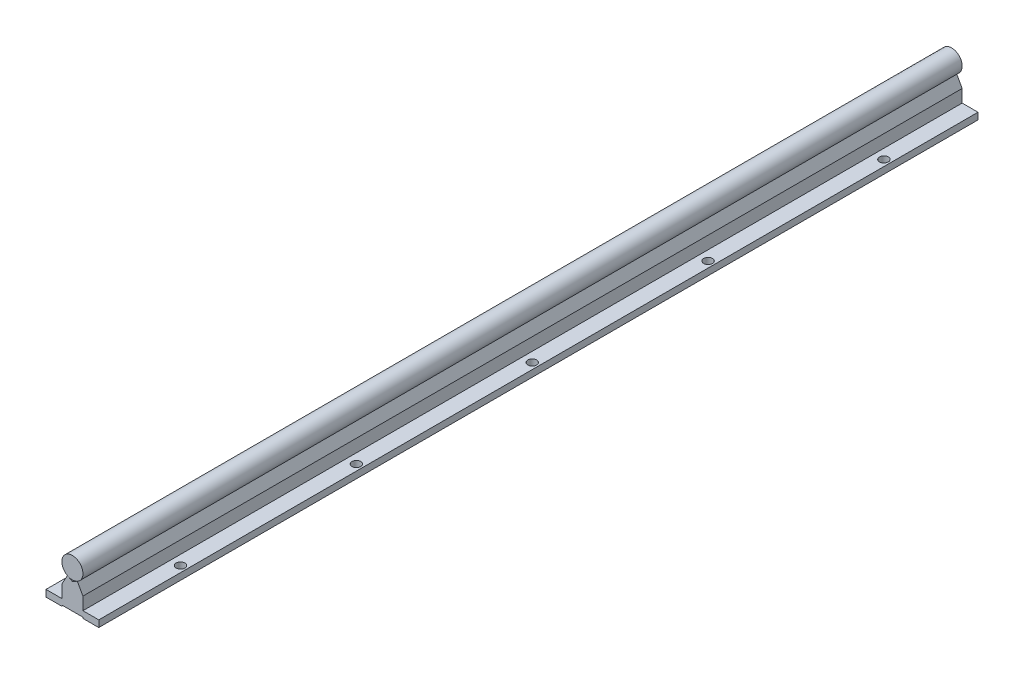
SolidWorks part; units mm, degrees
ref_plane "Alzado" through (0, 0, 0) normal (0, 0, 1) x (1, 0, 0)
ref_plane "Planta" through (0, 0, 0) normal (0, 1, 0) x (1, 0, 0)
ref_plane "Vista lateral" through (0, 0, 0) normal (1, 0, 0) x (0, 0, -1)
sketch "Croquis1" plane through (0, 0, 0) normal (0, 0, 1) x (1, 0, 0)
  line L0 (0, 0) -> (0, -22) construction
  line L1 (0, -22) -> (15, -22) construction
  line L2 (3.5, 0) -> (3.5, -22) construction
  line L3 (6, -22) -> (6, 5.4102) construction
  line L4 (-13.9204, -11) -> (10.0172, -11) construction
  line L5 (0, -6.8) -> (2.8235, -5.2941)
  line L6 (2.8235, -5.2941) -> (6, -11)
  line L7 (6, -11) -> (6, -18.2)
  line L8 (6, -18.2) -> (15, -18.2)
  line L9 (15, -18.2) -> (15, -22)
  line L10 (-6, -21.4) -> (6, -21.4)
  line L11 (6, -21.4) -> (6, -22)
  line L12 (6, -22) -> (15, -22)
  line L13 (-6, -21.4) -> (-6, -22)
  line L14 (-6, -22) -> (-15, -22)
  line L15 (-15, -18.2) -> (-15, -22)
  line L16 (-6, -18.2) -> (-15, -18.2)
  line L17 (-6, -11) -> (-6, -18.2)
  line L18 (-2.8235, -5.2941) -> (-6, -11)
  line L19 (0, -6.8) -> (-2.8235, -5.2941)
  circle A0 centre (0, 0) radius 6
  point P17 (0, -6)
  point P21 (0, -21.4)
  dimension "D1" = 12
  dimension "D2" = 22
  dimension "D3" = 15
  dimension "D4" = 3.5
  dimension "D5" = 6
  dimension "D6" = 11
  dimension "D7" = 0.8
  dimension "D8" = 3.8
  dimension "D9" = 0.6
extrude "Saliente-Extruir1" add sketch "Croquis1" along normal blind 500 contours L5 L19 L18 L17 L16 L15 L14 L13 L10 L11 L12 L9 L8 L7 L6 | A0 region at (0, -15.8774, 0) region at (0, 0, 0)
sketch "Croquis2" plane through (0, -18.2, 0) normal (0, 1, 0) x (1, 0, 0)
  line L0 (-11.5, 0) -> (-11.5, -500) construction
  line L1 (-6, 0) -> (-15, 0) construction
  line L2 (-6, -500) -> (-15, -500) construction
  line L3 (-15, -500) -> (-15, 0) construction
  circle A0 centre (-11.5, -50) radius 2.5
  circle A1 centre (-11.5, -150) radius 2.5
  circle A2 centre (-11.5, -250) radius 2.5
  circle A3 centre (-11.5, -350) radius 2.5
  circle A4 centre (-11.5, -450) radius 2.5
  dimension "D2" = 5
  dimension "D1" = 3.5
  dimension "D3" = 50
  dimension "D4" = 5
extrude "Cortar-Extruir1" cut sketch "Croquis2" against normal up to surface (3.8 mm away) up to face at (-10.5, -22, 250)
mirror "Simetría1" about plane through (0, 0, 0) normal (1, 0, 0) of "Cortar-Extruir1"
equation "\"D4@Croquis1\"=7/2"
